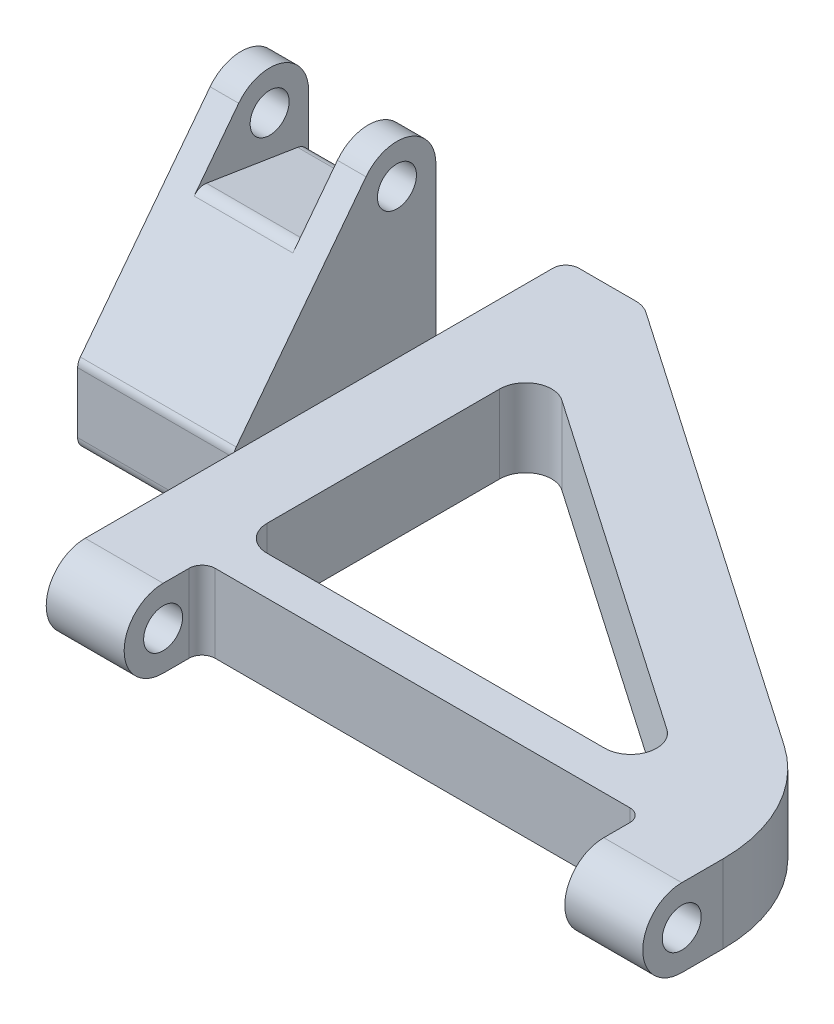
SolidWorks part; units mm, degrees
material "6061-T6 (SS)"
ref_plane "Front Plane" through (0, 0, 0) normal (0, 0, 1) x (1, 0, 0)
ref_plane "Top Plane" through (0, 0, 0) normal (0, 1, 0) x (1, 0, 0)
ref_plane "Right Plane" through (0, 0, 0) normal (1, 0, 0) x (0, 0, -1)
sketch "Sketch1" plane through (0, 0, 0) normal (0, 1, 0) x (1, 0, 0)
  line L1 (3.175, 0) -> (16.3997, 0)
  line L2 (0, -3.175) -> (0, -127)
  line L3 (0, -127) -> (19.05, -127)
  line L4 (19.05, -35.2194) -> (19.05, -92.075)
  line L5 (19.05, -127) -> (356.945, -127) construction
  line L6 (29.0026, -29.9903) -> (111.5275, -86.8459)
  line L7 (126.7387, -111.125) -> (126.7387, -127)
  line L8 (145.7887, -126.7288) -> (145.7887, -127)
  line L9 (126.7387, -127) -> (145.7887, -127)
  line L10 (123.5637, -107.95) -> (22.225, -107.95)
  line L11 (107.9249, -98.425) -> (25.4, -98.425)
  line L12 (19.05, -111.125) -> (19.05, -127)
  line L13 (9.7874, 0) -> (136.2637, -127)
  line L14 (9.7874, 0) -> (9.525, -127)
  line L15 (16.3997, 0) -> (19.05, 0)
  line L16 (145.7887, -127) -> (145.7887, -87.3167)
  line L17 (145.7887, -87.3167) -> (19.05, 0)
  arc A0 (29.0026, -29.9903) -> (19.05, -35.2194) centre (25.4, -35.2194) ccw
  arc A1 (111.5275, -86.8459) -> (107.9249, -98.425) centre (107.9249, -92.075) cw
  arc A2 (19.05, -92.075) -> (25.4, -98.425) centre (25.4, -92.075) ccw
  arc A3 (123.5637, -107.95) -> (126.7387, -111.125) centre (123.5637, -111.125) cw
  arc A4 (22.225, -107.95) -> (19.05, -111.125) centre (22.225, -111.125) ccw
  arc A7 (0, -3.175) -> (3.175, 0) centre (3.175, -3.175) cw
  point P22 (126.7387, -107.95)
  point P25 (19.05, -107.95)
  point P30 (19.05, 0)
  point P33 (0, 0)
  dimension "D7" = 6.35
  dimension "D9" = 6.35
  dimension "D10" = 3.175
  dimension "D11" = 45
  dimension "D12" = 19.05
  dimension "D13" = 3.175
  dimension "D1" = 127
  dimension "D2" = 19.05
  dimension "D3" = 19.05
  dimension "D4" = 107.6887
  dimension "D5" = 19.05
  dimension "D6" = 19.05
  dimension "D8" = 9.525
extrude "Boss-Extrude1" add sketch "Sketch1" along normal blind 19.05 contours A7 L2 L3 L14 L1 | A4 L10 L13 L11 A2 L4 A0 L6 L14 L3 L12 | L10 A3 L7 L13 L9 L8 L16 L17 L15 L1 L6 A1 L11 | L16 L17 L15 L1 A7 L2 L3 L12 A4 L10 A3 L7 L9 | L6 A1 L11 A2 L4 A0 region at (4.8357, 0, 63.3229) region at (94.8948, 0, 67.0253) region at (35.1815, 0, 27.8597)
sketch "Sketch7" plane through (0, 0, 0) normal (0, 0, -1) x (-1, 0, 0)
  line L1 (-3.175, 19.05) -> (-19.05, 19.05) construction
  line L2 (0, 19.05) -> (0, 0) construction
  circle A0 centre (-9.525, 9.525) radius 4.7625
  dimension "D1" = 9.525
  dimension "D2" = 9.525
  dimension "D3" = 9.525
extrude "Cut-Extrude7" cut sketch "Sketch7" against normal blind 38.1
fillet "Fillet4" radius 38.1 1 edges at (145.7887, 9.525, 87.3167)
fillet "Fillet5" radius 6.35 1 edges at (19.05, 9.525, 0)
sketch "Sketch8" plane through (0, 0, 0) normal (-1, 0, 0) x (0, 0, 1)
  line L0 (127, 19.05) -> (127, 0) construction
  line L1 (3.175, 19.05) -> (127, 19.05) construction
  circle A0 centre (117.475, 9.525) radius 4.7625
  dimension "D1" = 9.525
  dimension "D2" = 9.525
  dimension "D3" = 9.525
extrude "Cut-Extrude8" cut sketch "Sketch8" against normal through all
fillet "Fillet6" 2 edges at (9.525, 19.05, 127) (9.525, 0, 127) type full round first side face at (64.4623, 19.05, 80.6757) second side face at (64.4623, 0, 80.6757) middle face at (9.525, 9.525, 127)
fillet "Fillet7" 2 edges at (136.2637, 19.05, 127) (136.2637, 0, 127) type full round first side face at (64.4623, 19.05, 79.315) second side face at (64.4623, 0, 79.315) middle face at (136.2637, 9.525, 127)
sketch "Sketch9" plane through (0, 19.05, 0) normal (0, 1, 0) x (1, 0, 0)
  line L0 (6.985, -44.45) -> (12.065, -44.45)
  line L3 (14.2875, -38.1) -> (4.7625, -38.1) construction
  line L5 (12.065, -106.045) -> (6.985, -106.045)
  line L9 (15.24, -35.2194) -> (15.24, -92.075)
  line L10 (15.24, -47.625) -> (15.24, -92.075)
  line L11 (15.24, -92.075) -> (15.24, -102.87)
  line L12 (3.81, -3.175) -> (3.81, -117.475)
  line L13 (3.81, -47.625) -> (3.81, -102.87)
  arc A0 (3.81, -102.87) -> (6.985, -106.045) centre (6.985, -102.87) ccw
  arc A1 (12.065, -106.045) -> (15.24, -102.87) centre (12.065, -102.87) ccw
  arc A2 (12.065, -44.45) -> (15.24, -47.625) centre (12.065, -47.625) cw
  arc A3 (3.81, -47.625) -> (6.985, -44.45) centre (6.985, -47.625) cw
  point P8 (22.225, -107.95)
  point P9 (0, -107.95)
  point P11 (22.225, -106.045)
  point P12 (0, -106.045)
  point P13 (22.225, -109.855)
  point P14 (0, -109.855)
  dimension "D2" = 3.175
  dimension "D1" = 6.35
  dimension "D4" = 3.81
  dimension "D5" = 3.81
extrude "Cut-Extrude9" cut sketch "Sketch9" along normal blind 12.7 from surface starting at face at (64.4623, 0, 77.9543)
sketch "Sketch10" plane through (0, 19.05, 0) normal (0, 1, 0) x (1, 0, 0)
  line L0 (20.6375, -11.7634) -> (20.6375, -17.9323)
  line L1 (14.2875, -38.1) -> (14.2875, 0) construction
  line L2 (25.6138, -9.1488) -> (69.9263, -39.6779)
  line L3 (123.4186, -80.3871) -> (120.5366, -84.5704)
  line L4 (116.1207, -85.3836) -> (71.8082, -54.8545)
  line L5 (129.3043, -75.9598) -> (20.6769, -1.1209) construction
  line L6 (29.0026, -29.9903) -> (111.5275, -86.8459) construction
  line L7 (63.4416, -49.0904) -> (22.0112, -20.5469)
  line L8 (70.7396, -44.0938) -> (67.8575, -48.2771)
  line L9 (73.877, -46.2554) -> (70.9949, -50.4387)
  line L10 (78.2929, -45.4421) -> (122.6054, -75.9712)
  arc A0 (122.6054, -75.9712) -> (123.4186, -80.3871) centre (120.8041, -78.5858) cw
  arc A1 (120.5366, -84.5704) -> (116.1207, -85.3836) centre (117.922, -82.7691) cw
  arc A2 (22.0112, -20.5469) -> (20.6375, -17.9323) centre (23.8125, -17.9323) cw
  arc A3 (20.6375, -11.7634) -> (25.6138, -9.1488) centre (23.8125, -11.7634) cw
  arc A4 (70.9949, -50.4387) -> (71.8082, -54.8545) centre (73.6095, -52.24) ccw
  arc A5 (73.877, -46.2554) -> (78.2929, -45.4421) centre (76.4916, -48.0567) cw
  arc A6 (70.7396, -44.0938) -> (69.9263, -39.6779) centre (68.125, -42.2925) ccw
  arc A7 (67.8575, -48.2771) -> (63.4416, -49.0904) centre (65.2429, -46.4758) cw
  point P13 (125.22, -77.7725)
  point P20 (20.6375, -5.7204)
  dimension "D5" = 3.175
  dimension "D6" = 3.175
  dimension "D1" = 6.35
  dimension "D2" = 127
  dimension "D3" = 3.81
  dimension "D4" = 3.81
extrude "Cut-Extrude10" cut sketch "Sketch10" along normal blind 12.7 from surface starting at face at (9.525, 0, 75.2475)
sketch "Sketch11" plane through (0, 19.05, 0) normal (0, 1, 0) x (1, 0, 0)
  line L0 (117.7237, -104.14) -> (138.0437, -104.14)
  line L1 (140.8273, -99.4378) -> (131.8193, -83.0187)
  line L2 (126.4211, -82.7446) -> (115.1092, -99.1637)
  line L3 (120.5366, -84.5704) -> (123.4186, -80.3871) construction
  line L4 (123.5637, -107.95) -> (22.225, -107.95) construction
  arc A0 (117.7237, -104.14) -> (115.1092, -99.1637) centre (117.7237, -100.965) cw
  arc A1 (131.8193, -83.0187) -> (126.4211, -82.7446) centre (129.0357, -84.5459) ccw
  arc A2 (140.8273, -99.4378) -> (138.0437, -104.14) centre (138.0437, -100.965) cw
  dimension "D1" = 3.175
  dimension "D2" = 3.81
  dimension "D3" = 20.32
  dimension "D4" = 3.81
extrude "Cut-Extrude11" cut sketch "Sketch11" along normal blind 12.7 from surface contours L1 A1 L2 A0 L0 A2 starting at face at (45.1044, 0, 29.9928)
sketch "Sketch12" plane through (0, 0, 0) normal (-1, 0, 0) x (0, 0, 1)
  line L0 (117.475, 9.525) -> (117.475, 181.737)
  line L1 (117.475, 181.737) -> (41.2863, 55.4376)
  line L2 (31.7613, 55.4376) -> (31.7613, 0)
  line L3 (3.175, 0) -> (117.475, 0) construction
  line L4 (48.843, 61.2361) -> (81.2135, 19.05)
  line L5 (31.7613, 0) -> (81.2135, 0)
  line L6 (3.175, 19.05) -> (117.475, 19.05) construction
  line L7 (3.175, 19.05) -> (117.475, 19.05)
  line L8 (81.2135, 19.05) -> (81.2135, 0)
  circle A0 centre (41.2863, 55.4376) radius 4.7625
  arc A1 (48.843, 61.2361) -> (31.7613, 55.4376) centre (41.2863, 55.4376) ccw
  line M11 (3.175, 0) -> (117.475, 0)
  line M13 (117.475, 19.05) -> (3.175, 19.05)
  dimension "D4" = 9.525
  dimension "D5" = 19.05
  dimension "D1" = 172.212
  dimension "D2" = 147.5
  dimension "D3" = 31.1
  dimension "D6" = 37.5
extrude "Boss-Extrude2" add sketch "Sketch12" along normal blind 38.1 contours L4 A1 A0 L2 M13 | L8 L2 M13 M11 region at (0, 36.4342, 49.95) region at (0, 9.525, 56.4874)
sketch "Sketch13" plane through (-38.1, 0, 0) normal (-1, 0, 0) x (0, 0, 1)
  line L0 (37.6118, 42.9083) -> (54.7178, 45.6333)
  line L1 (31.7613, 44.2751) -> (58.5794, 48.5473)
  line L2 (31.7613, 55.4376) -> (31.7613, 0) construction
  line L3 (39.1169, 8.239) -> (58.6719, 34.656)
  line L4 (64.119, 34.0702) -> (76.0099, 7.6532)
  line L5 (34.9363, 55.4376) -> (34.9363, 0)
  line L6 (34.9363, 39.7728) -> (34.9363, 18.1344)
  line L7 (48.843, 61.2361) -> (81.2135, 19.05) construction
  line L8 (31.7613, 3.175) -> (81.2135, 3.175)
  line L9 (41.6688, 3.175) -> (73.1147, 3.175)
  line L10 (31.7613, 44.2751) -> (31.7613, 55.4376)
  line L11 (46.3241, 59.3032) -> (78.6946, 17.1172)
  line L12 (55.0133, 47.9792) -> (78.6946, 17.1172)
  line L13 (57.8158, 40.6734) -> (40.7098, 16.31)
  line L14 (78.0385, 19.05) -> (78.0385, 0)
  line L15 (78.0385, 19.05) -> (78.0385, 0)
  line L16 (58.5794, 48.5473) -> (48.843, 61.2361)
  circle A0 centre (41.2863, 55.4376) radius 4.7625 construction
  circle A1 centre (41.2863, 55.4376) radius 4.7625
  arc A2 (48.843, 61.2361) -> (31.7613, 55.4376) centre (41.2863, 55.4376) ccw
  arc A3 (57.8158, 40.6734) -> (54.7178, 45.6333) centre (55.2173, 42.4979) ccw
  arc A4 (34.9363, 39.7728) -> (37.6118, 42.9083) centre (38.1113, 39.7728) cw
  arc A5 (34.9363, 18.1344) -> (40.7098, 16.31) centre (38.1113, 18.1344) ccw
  arc A6 (58.6719, 34.656) -> (64.119, 34.0702) centre (61.2238, 32.767) cw
  arc A7 (41.6688, 3.175) -> (39.1169, 8.239) centre (41.6688, 6.35) cw
  arc A8 (73.1147, 3.175) -> (76.0099, 7.6532) centre (73.1147, 6.35) ccw
  point P28 (61.8953, 39.0105)
  circle M17 centre (41.2863, 55.4376) radius 4.7625
  line M18 (81.2135, 19.05) -> (48.843, 61.2361)
  arc M19 (48.843, 61.2361) -> (31.7613, 55.4376) centre (41.2863, 55.4376) ccw
  line M20 (31.7613, 55.4376) -> (31.7613, 0)
  dimension "D1" = 3.175
  dimension "D5" = 19.05
  dimension "D6" = 3.175
  dimension "D7" = 3.175
  dimension "D8" = 3.175
  dimension "D9" = 3.175
  dimension "D10" = 3.175
  dimension "D11" = 3.175
  dimension "D2" = 3.175
  dimension "D3" = 3.175
  dimension "D4" = 3.175
extrude "Cut-Extrude12" cut sketch "Sketch13" against normal blind 34.925 contours L6 A5 L13 A3 L0 A4 | L9 A8 L4 A6 L3 A7 region at (-38.1, 32.9384, 43.9416) region at (-38.1, 15.1335, 58.5121)
extrude "Cut-Extrude13" cut sketch "Sketch13<4>" against normal blind 24.13 from offset 6.985 contours A2 M20 M18 M19 M17 region at (-38.1, 44.8625, 33.2955) offset against normal yes
sketch "Sketch13<4>" plane through (-38.1, 0, 0) normal (-1, 0, 0) x (0, 0, 1) same geometry as "Sketch13"
fillet "Fillet13" radius 3.175 2 edges at (-19.05, 44.2751, 31.7613) (-19.05, 48.5473, 58.5794)
fillet "Fillet14" radius 3.175 1 edges at (-19.05, 0, 31.7613)
fillet "Fillet15" radius 3.175 2 edges at (-19.05, 19.05, 81.2135) (-19.05, 0, 81.2135)
move or copy body "Body-Move/Copy2" [suppressed] bodies to move or copy 113
move or copy body "Body-Move/Copy1" [suppressed] bodies to move or copy 113
